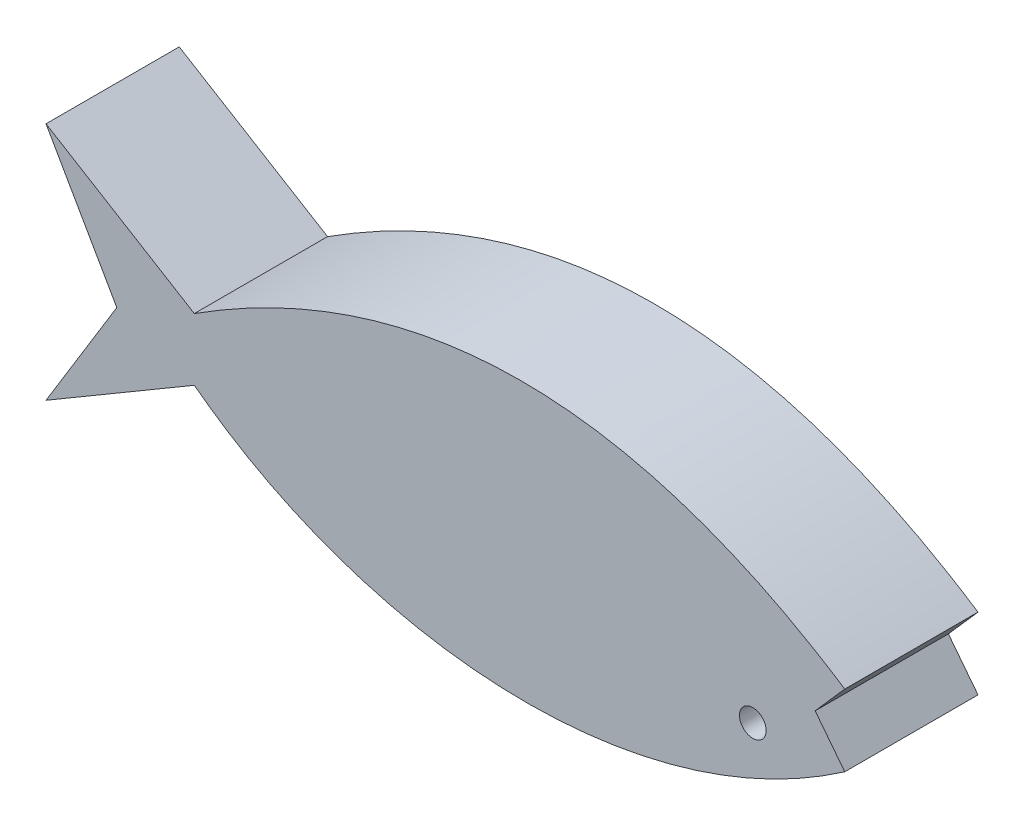
SolidWorks part; units mm, degrees
ref_plane "Front" through (0, 0, 0) normal (0, 0, 1) x (1, 0, 0)
ref_plane "Top" through (0, 0, 0) normal (0, 1, 0) x (1, 0, 0)
ref_plane "Right" through (0, 0, 0) normal (1, 0, 0) x (0, 0, -1)
sketch "Sketch2" plane through (0, 0, 0) normal (0, 0, -1) x (1, 0, 0)
  line L0 (29.973, 6.6427) -> (28.8624, 5.2157)
  line L1 (28.8624, 5.2157) -> (29.973, 3.9538)
  line L2 (5.5653, 6.2857) -> (0, 9.5561)
  line L3 (0, 9.5561) -> (2.6565, 5.2157)
  line L4 (2.6565, 5.2157) -> (0, 0.5701)
  line L5 (0, 0.5701) -> (5.5653, 3.9538)
  circle A0 centre (26.5226, 6.7807) radius 0.5001
  spline S0 degree 3 poles (5.5653, 6.2857) (12.0373, 11.2173) (22.1418, 12.0787) (29.973, 6.6427) knots 0 0 0 0 1 1 1 1
  spline S1 degree 2 poles (5.5653, 3.9538) (17.9191, -3.9397) (29.973, 3.9538) knots 0 0 0 1 1 1
extrude "Boss-Extrude1" add sketch "Sketch2" along normal blind 5
ref_plane "Fish Top Plane" through (0, 0, -5) normal (0, 0, -1) x (1, 0, 0)
sketch "Sketch6" plane through (0, 0, -5) normal (0, 0, -1) x (1, 0, 0)
  line L0 (15.3979, 9.0108) -> (15.7143, 6.4347)
  line L1 (19.966, 8.9) -> (19.5228, 6.4347)
  line L2 (16.9562, 6.0606) -> (18.7239, 5.9471)
  spline S0 degree 3 poles (15.3979, 9.0108) (12.9599, 8.5403) (12.692, 6.001) (12.7621, 5.0248) knots 0 0 0 0 1 1 1 1
  spline S1 degree 3 poles (12.7621, 5.0248) (12.8121, 3.4578) (13.8829, 1.4124) (15.7143, 1.3634) knots 0 0 0 0 1 1 1 1
  spline S2 degree 2 poles (15.7143, 1.3634) (17.3719, 1.2363) (18.1133, 3.0916) knots 0 0 0 1 1 1
  spline S3 degree 3 poles (18.1133, 3.0916) (18.8878, 1.3279) (22.1478, 1.0004) (22.4262, 5.0248) knots 0 0 0 0 1 1 1 1
  spline S4 degree 3 poles (22.4262, 5.0248) (22.6023, 7.0926) (21.5883, 8.4517) (19.966, 8.9) knots 0 0 0 0 1 1 1 1
  spline S5 degree 3 poles (18.7239, 5.9471) (18.6946, 5.4325) (18.8967, 3.9907) (20.3079, 4.5183) knots 0 0 0 0 1 1 1 1
  spline S6 degree 3 poles (20.3079, 4.5183) (21.1248, 4.9718) (20.8007, 6.5464) (19.5228, 6.4347) knots 0 0 0 0 1 1 1 1
  spline S7 degree 3 poles (15.7143, 6.4347) (15.0974, 6.367) (14.3794, 6.1913) (14.2889, 5.2367) knots 0 0 0 0 1 1 1 1
  spline S8 degree 3 poles (14.2889, 5.2367) (14.2577, 4.5676) (14.8083, 4.0147) (15.8706, 3.9973) knots 0 0 0 0 1 1 1 1
  spline S9 degree 3 poles (15.8706, 3.9973) (16.6437, 3.9179) (17.4186, 4.5598) (16.9562, 6.0606) knots 0 0 0 0 1 1 1 1
extrude "Boss-Extrude2" add sketch "Sketch6" along normal blind 1
